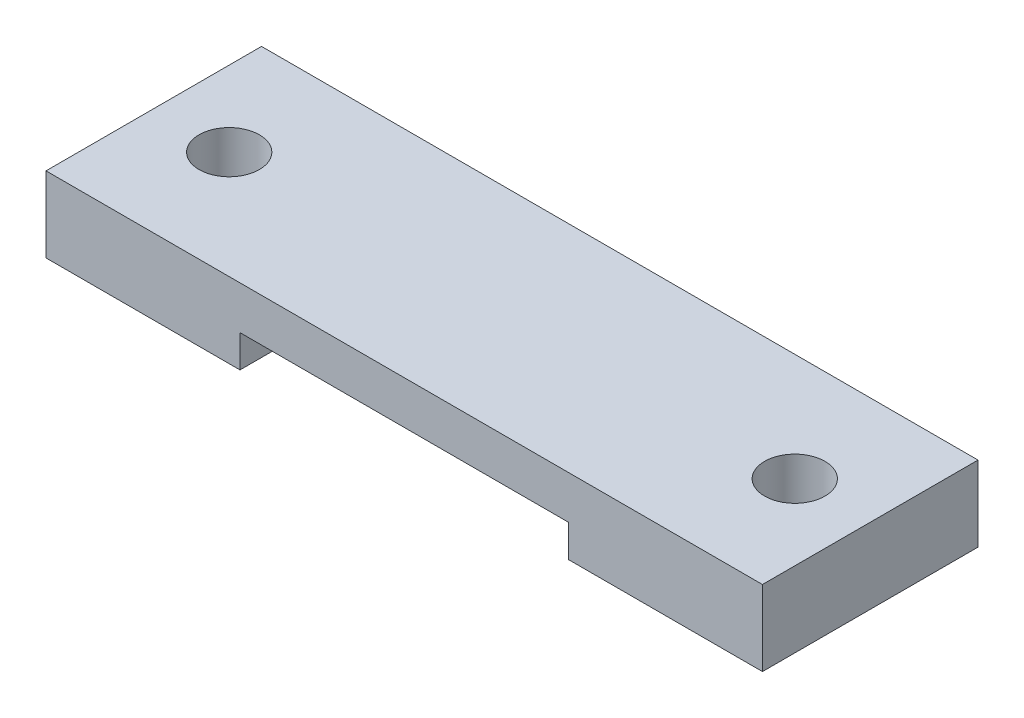
SolidWorks part; units mm, degrees
ref_plane "Front Plane" through (0, 0, 0) normal (0, 0, 1) x (1, 0, 0)
ref_plane "Top Plane" through (0, 0, 0) normal (0, 1, 0) x (1, 0, 0)
ref_plane "Right Plane" through (0, 0, 0) normal (1, 0, 0) x (0, 0, -1)
sketch "Sketch1" plane through (0, 0, 0) normal (0, 1, 0) x (1, 0, 0)
  line L0 (-55, 0) -> (55, 0) construction
  line L1 (-7.62, -5) -> (7.62, -5)
  line L2 (-7.62, -5) -> (-7.62, 5)
  line L3 (-7.62, 5) -> (7.62, 5)
  line L4 (7.62, -5) -> (7.62, 5)
  line L5 (-7.62, -5) -> (7.62, 5) construction
  line L6 (-7.62, 5) -> (7.62, -5) construction
  line L7 (-7.62, 5) -> (-16.62, 5)
  line L8 (-7.62, 5) -> (-7.62, -5)
  line L9 (-7.62, -5) -> (-16.62, -5)
  line L10 (-16.62, 5) -> (-16.62, -5)
  line L11 (7.62, 5) -> (16.62, 5)
  line L12 (7.62, 5) -> (7.62, -5)
  line L13 (7.62, -5) -> (16.62, -5)
  line L14 (16.62, 5) -> (16.62, -5)
  circle A0 centre (-13.12, 0) radius 1.4
  circle A1 centre (13.12, 0) radius 1.4
  point P0 (0, 0)
  dimension "D4" = 2.8
  dimension "D1" = 15.24
  dimension "D2" = 10
  dimension "D5" = 3.5
  dimension "D6" = 3.5
  dimension "D7" = 33.24
extrude "Boss-Extrude1" add sketch "Sketch1" against normal blind 3.5 contours L7 L10 L9 L2 A0 | L14 L11 L4 L13 A1 region at (-12.12, 0, 4.8655) region at (7.7545, 0, 0)
extrude "Boss-Extrude2" add sketch "Sketch1<3>" against normal blind 2 contours L1 L4 L3 L2 region at (0, 0, 0)
sketch "Sketch1<3>" plane through (0, 0, 0) normal (0, 1, 0) x (1, 0, 0) same geometry as "Sketch1"
